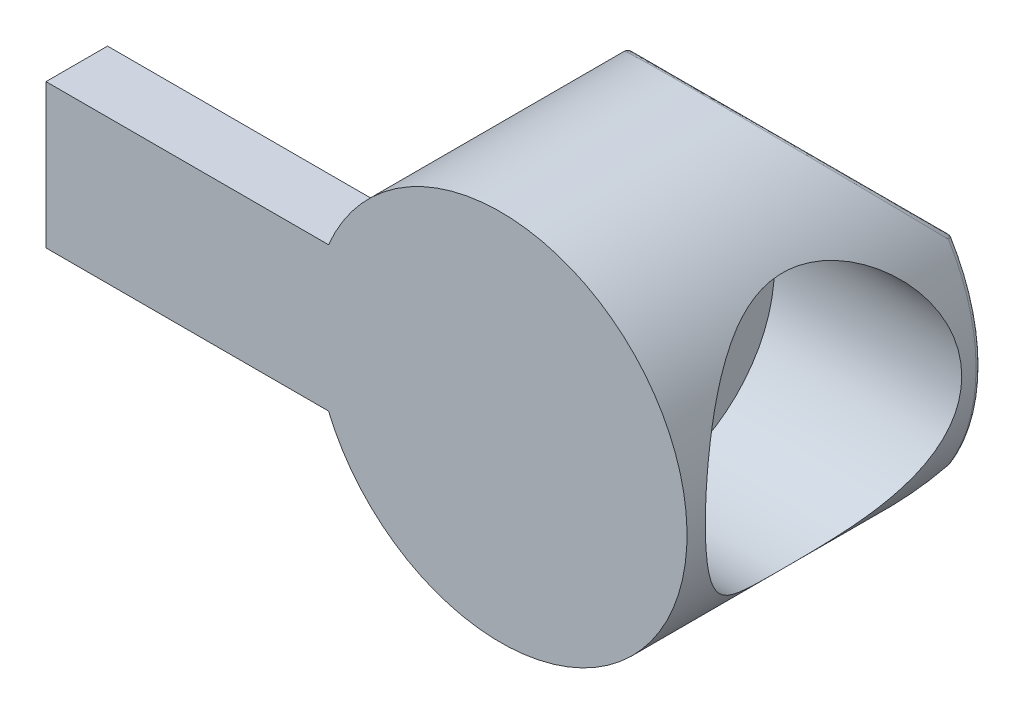
SolidWorks part; units mm, degrees
note: The reader was unsure of these and kept them because the rebuilt part matched: shared geometry of "Sketch1<3>", "Sketch2<3>", "Sketch2<4>".
ref_plane "Front"
ref_plane "Top" through (0, 0, 0) normal (0, 1, 0) x (1, 0, 0)
ref_plane "Right" through (0, 0, 0) normal (1, 0, 0) x (0, 0, -1)
sketch "Sketch1" plane through (0, 0, 0) normal (0, 0, 1) x (1, 0, 0)
  line L0 (10.16, 0) -> (-49.0838, 0) construction
  line L1 (0, 3.9243) -> (-24.765, 3.9243)
  line L2 (0, -3.9243) -> (-24.765, -3.9243)
  line L3 (0, 3.9243) -> (0, -3.9243)
  line L4 (-24.765, 3.9243) -> (-24.765, -3.9243)
  circle A0 centre (0, 0) radius 10.16
  arc A1 (-10.16, 0) -> (-9.3715, 3.9243) centre (0, 0) ccw
  dimension "PART DIA" = 20.32
  dimension "ARM WIDTH" = 7.8486
  dimension "ARM LENGTH" = 34.925
extrude "PART DIA EXTRUDE" add sketch "Sketch1" against normal blind 16.002 contours A0
extrude "ARM EXTRUDE" add sketch "Sketch1<3>" against normal blind 3.3528 contours L2 L4 L1 L3
sketch "Sketch1<3>" plane through (0, 0, 0) normal (0, 0, 1) x (1, 0, 0) same geometry as "Sketch1"
ref_plane "Plane1" through (10.16, 0, 0) normal (1, 0, 0) x (0, 0, -1)
sketch "Sketch2" plane through (10.16, 0, 0) normal (1, 0, 0) x (0, 0, -1)
  line L0 (16.002, 0) -> (0, 0) construction
  line L1 (0, 10.16) -> (0, -10.16) construction
  line L2 (11.1361, 10.16) -> (16.002, 10.16)
  line L3 (7.9833, 0) -> (22.1985, 0) construction
  line L4 (16.002, 10.16) -> (16.002, 5.2941)
  line L5 (16.002, -10.16) -> (16.002, 10.16) construction
  line L6 (16.002, 5.2941) -> (11.1361, 10.16)
  line L7 (16.002, -10.16) -> (16.002, -5.2941)
  line L8 (11.1361, -10.16) -> (16.002, -10.16)
  line L9 (16.002, -5.2941) -> (11.1361, -10.16)
  circle A0 centre (7.9833, 0) radius 6.985
  circle A1 centre (7.9833, 0) radius 4.1656
  dimension "D1" = 10.16
  dimension "CBORE DIA" = 13.97
  dimension "THRU HOLE" = 8.3312
  dimension "D2" = 45
  dimension "CL OF HOLE" = 7.9833
  dimension "D3" = 4.8659
  dimension "D4" = 4.8659
extrude "CBORE EXTRUDE" cut sketch "Sketch2" against normal blind 10.2108 contours A0
extrude "THRU HOLE-Extrude2" cut sketch "Sketch2<3>" against normal through all contours A1
sketch "Sketch2<3>" plane through (10.16, 0, 0) normal (1, 0, 0) x (0, 0, -1) same geometry as "Sketch2"
extrude "ANGLE-Extrude3" cut sketch "Sketch2<4>" against normal through all contours L6 L2 L4 | L9 L8 L7
sketch "Sketch2<4>" plane through (10.16, 0, 0) normal (1, 0, 0) x (0, 0, -1) same geometry as "Sketch2"
hole_wizard "#10-32 Tapped Hole1" [suppressed] positions "Sketch6" profile "Sketch5" tap size "#10-32" standard "Ansi Inch"
sketch "Sketch6" plane through (6.985, 0, 0) normal (1, 0, 0) x (0, 0, -1)
  circle A0 centre (5.2578, 0) radius 2.0447 construction
  point P1 (5.2578, 0)
sketch "Sketch5" plane through (6.985, 0, -5.2578) normal (0, 1, 0) x (0, 0, -1)
  line L0 (0, 0) -> (0, 13.97)
  line L1 (0, 13.97) -> (2.0193, 13.97)
  line L2 (2.0193, 13.97) -> (2.0193, 0)
  line L5 (2.0193, 0) -> (0, 0)
  line L11 (0, -6.35) -> (0, 107.95) construction
  dimension "Thru Tap Drill Dia." = 4.0386
  dimension "Thru Tap Drill Depth" = 13.97
chamfer "Chamfer2" [suppressed] distance 0.508 angle 45
hole_wizard "M5x0.8 Tapped Hole1" [suppressed] positions "Sketch8" profile "Sketch9" tap size "M5x0.8" standard "Ansi Metric"
sketch "Sketch8" plane through (10.16, 0, 0) normal (1, 0, 0) x (0, 0, -1)
  point P1 (7.9833, 0)
sketch "Sketch9" plane through (10.16, 0, -7.9833) normal (0, 1, 0) x (0, 0, -1)
  line L0 (0, 0) -> (0, 20.32)
  line L1 (0, 20.32) -> (2.1, 20.32)
  line L2 (2.1, 20.32) -> (2.1, 0)
  line L5 (2.1, 0) -> (0, 0)
  line L11 (0, -6.35) -> (0, 107.95) construction
  dimension "Thru Tap Drill Dia." = 4.2
  dimension "Thru Tap Drill Depth" = 20.32
chamfer "Chamfer3" [suppressed] distance 0.508 angle 45
hole_wizard "5/16-18 Tapped Hole1" [suppressed] positions "Sketch11" profile "Sketch10" tap size "5/16-18" standard "Ansi Inch"
sketch "Sketch11" plane through (10.16, 0, 0) normal (1, 0, 0) x (0, 0, -1)
  point P1 (7.9833, 0)
sketch "Sketch10" plane through (10.16, 0, -7.9833) normal (0, 1, 0) x (0, 0, -1)
  line L0 (0, 0) -> (0, 20.32)
  line L1 (0, 20.32) -> (3.2639, 20.32)
  line L2 (3.2639, 20.32) -> (3.2639, 0)
  line L5 (3.2639, 0) -> (0, 0)
  line L11 (0, -6.35) -> (0, 107.95) construction
  dimension "Thru Tap Drill Dia." = 6.5278
  dimension "Thru Tap Drill Depth" = 20.32
chamfer "Chamfer4" [suppressed] distance 0.508 angle 45
hole_wizard "M8x1.25 Tapped Hole1" [suppressed] positions "Sketch13" profile "Sketch12" tap size "M8x1.25" standard "Ansi Metric"
sketch "Sketch13" plane through (10.16, 0, 0) normal (1, 0, 0) x (0, 0, -1)
  point P1 (7.9833, 0)
sketch "Sketch12" plane through (10.16, 0, -7.9833) normal (0, 1, 0) x (0, 0, -1)
  line L0 (0, 0) -> (0, 20.3155)
  line L1 (0, 20.3155) -> (3.4, 20.3155)
  line L2 (3.4, 20.3155) -> (3.4, 0)
  line L5 (3.4, 0) -> (0, 0)
  line L11 (0, -6.35) -> (0, 107.95) construction
  dimension "Thru Tap Drill Dia." = 6.8
  dimension "Thru Tap Drill Depth" = 20.3155
chamfer "Chamfer5" [suppressed] distance 0.508 angle 45
fillet "Fillet1" radius 0.254 6 edges at (10.16, 0, -16.002) (-10.16, 0, -16.002) (0, -10.16, -11.1361) (0, -5.2941, -16.002) (0, 5.2941, -16.002) (0, 10.16, -11.1361)
